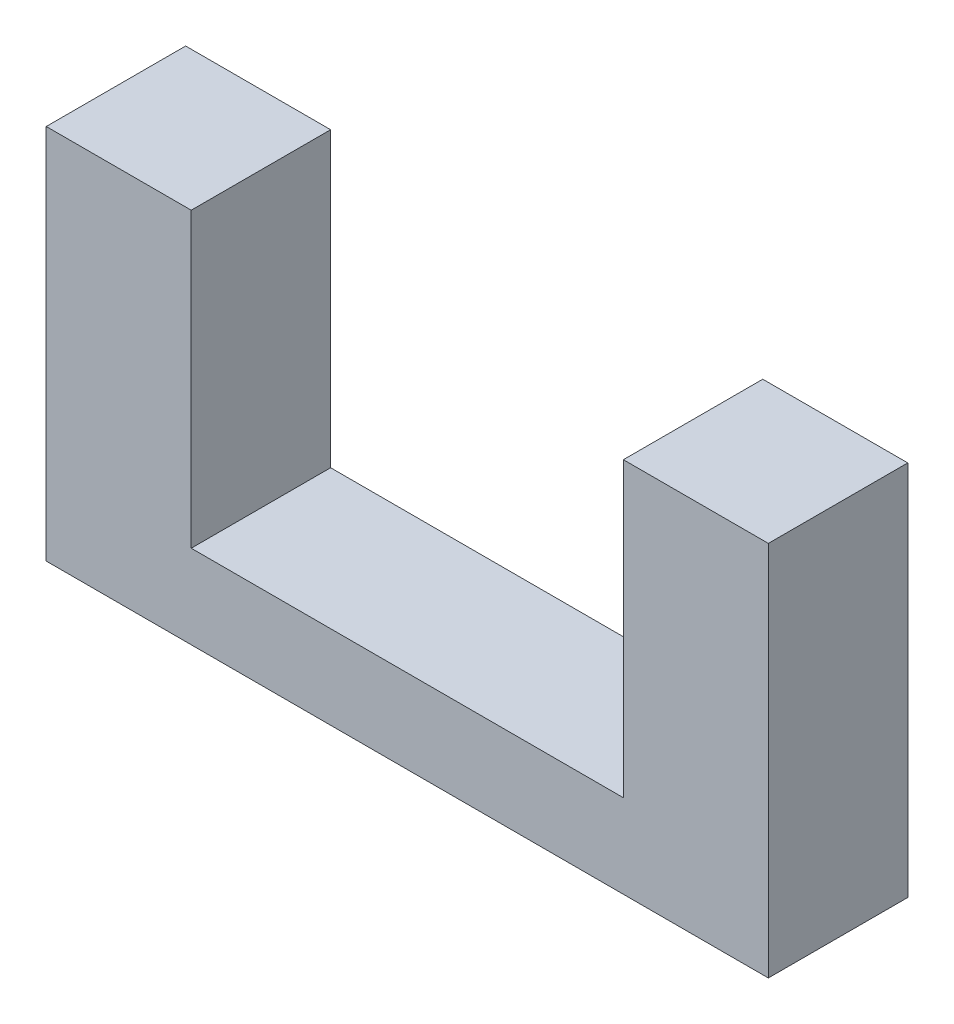
SolidWorks part; units mm, degrees
ref_plane "XY" through (0, 0, 0) normal (0, 0, 1) x (1, 0, 0)
ref_plane "XZ" through (0, 0, 0) normal (0, 1, 0) x (1, 0, 0)
ref_plane "YZ" through (0, 0, 0) normal (1, 0, 0) x (0, 0, -1)
ref_axis "X" through (-88.99, 0, 0) along (1, 0, 0)
ref_axis "Y" through (0, -55, 0) along (0, 1, 0)
ref_axis "Z" through (0, 0, 55) along (0, 0, -1)
sketch "Sketch1" plane through (0, 0, 0) normal (0, 0, 1) x (1, 0, 0)
  line L0 (-15.5, 13.5) -> (-15.5, -7.5)
  line L5 (-25.9, -13.5) -> (25.9, -13.5)
  line L6 (-25.9, -13.5) -> (-25.9, 13.5)
  line L7 (-25.9, 13.5) -> (-15.5, 13.5)
  line L8 (25.9, -13.5) -> (25.9, 13.5)
  line L9 (-25.9, -13.5) -> (25.9, 13.5) construction
  line L10 (-25.9, 13.5) -> (25.9, -13.5) construction
  line L11 (-15.5, -7.5) -> (15.5, -7.5)
  line L12 (15.5, -7.5) -> (15.5, 13.5)
  line L13 (0, 0) -> (0, -7.5) construction
  line L14 (15.5, 13.5) -> (25.9, 13.5)
  point P0 (0, 0)
  dimension "D1" = 51.8
  dimension "D2" = 31
  dimension "D3" = 21
  dimension "D4" = 6
extrude "Boss-Extrude1" add sketch "Sketch1" along normal blind 10
